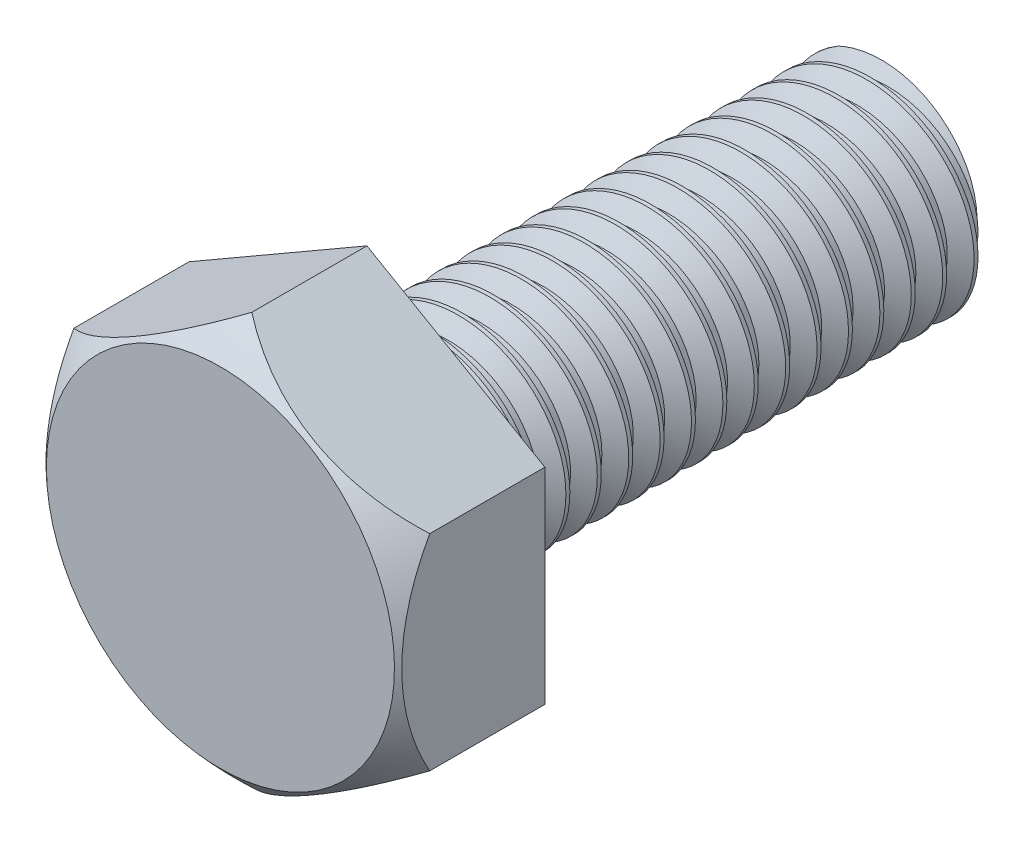
SolidWorks part; units mm, degrees
ref_plane "Front Plane" through (0, 0, 0) normal (0, 0, 1) x (1, 0, 0)
ref_plane "Top Plane" through (0, 0, 0) normal (0, 1, 0) x (1, 0, 0)
ref_plane "Right Plane" through (0, 0, 0) normal (1, 0, 0) x (0, 0, -1)
sketch "Sketch1" plane through (0, 0, 0) normal (0, 0, 1) x (1, 0, 0)
  circle A0 centre (0, 0) radius 5
  dimension "D1" = 10
extrude "Boss-Extrude1" add sketch "Sketch1" along normal blind 25
sketch "Sketch2" plane through (0, 0, 25) normal (0, 0, 1) x (1, 0, 0)
  line L1 (0, -9.815) -> (8.5, -4.9075)
  line L2 (8.5, -4.9075) -> (8.5, 4.9075)
  line L3 (8.5, 4.9075) -> (0, 9.815)
  line L4 (0, 9.815) -> (-8.5, 4.9075)
  line L5 (-8.5, 4.9075) -> (-8.5, -4.9075)
  line L6 (-8.5, -4.9075) -> (0, -9.815)
  circle A0 centre (0, 0) radius 8.5 construction
  dimension "D1" = 17
extrude "Boss-Extrude2" add sketch "Sketch2" along normal blind 7
sketch "Sketch3" plane through (0, 0, 0) normal (1, 0, 0) x (0, 0, -1)
  line L0 (-32, 4.9075) -> (-32, 9.815) construction
  line L1 (-32, 9.815) -> (-25, 9.815) construction
  line L2 (-30.5, 9.815) -> (-32, 9.815)
  line L3 (-32, 9.815) -> (-32, 8.315)
  line L4 (-32, 0) -> (-65.6884, 0) construction
  line L5 (-32, -4.9075) -> (-32, 4.9075) construction
  arc A0 (-32, 8.315) -> (-30.5, 9.815) centre (-18.5442, -3.6409) cw
  dimension "D1" = 18
  dimension "D2" = 1.5
  dimension "D3" = 1.5
revolve "Cut-Revolve1" cut sketch "Sketch3" angle 360 about L4
thread "Thread1" pitch 1.5 method cut profile "Thread Profile1" start angle 0, offset 2, length 25, pitch 1.5, diameter 10
ref_plane "Plane1" through (5, 0, -2) normal (0, -1, 0) x (1, 0, 0)
sketch "Thread Profile1" plane through (5, 0, -2) normal (0, -1, 0) x (1, 0, 0)
  line L0 (0, 0) -> (0, 1.5) construction
  line L11 (0, 0) -> (0, 1.3125)
  line L12 (0, 1.3125) -> (-0.8119, 0.8437)
  line L13 (-0.8119, 0.8437) -> (-0.8119, 0.4687)
  line L15 (-0.8119, 0.4687) -> (0, 0)
  line L17 (-0.8119, 0.6562) -> (0, 0.6562) construction
  point P2 (0, 0)
  dimension "Pitch" = 1.5
  dimension "Profile_Angle" = 60
  dimension "Profile_Land" = 0.375
  dimension "Profile_Height" = 0.8119
